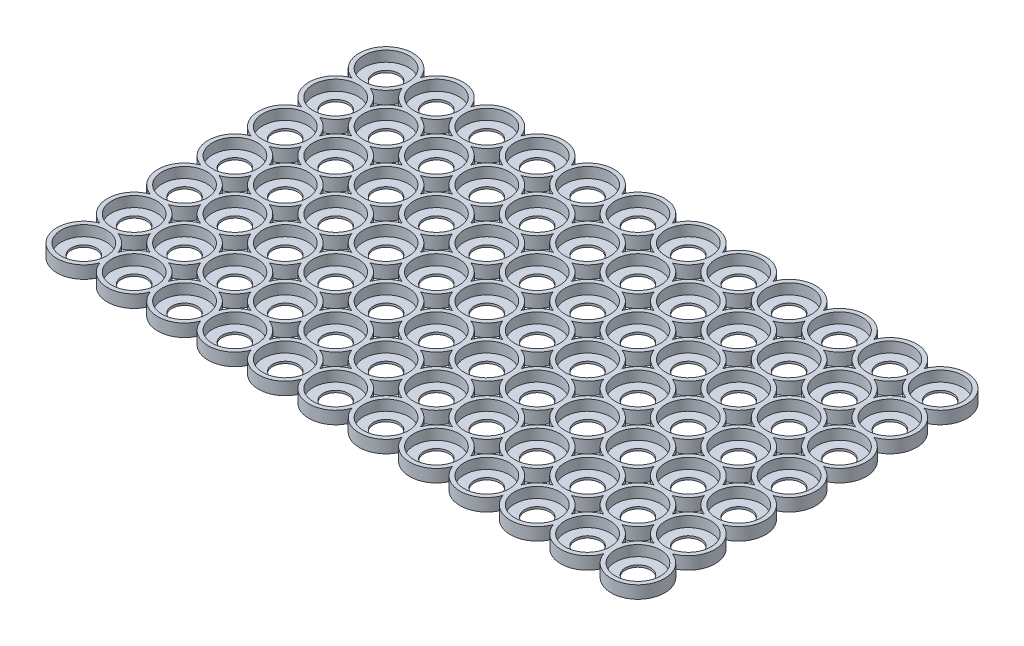
SolidWorks part; units mm, degrees
ref_plane "Front Plane" through (0, 0, 0) normal (0, 0, 1) x (1, 0, 0)
ref_plane "Top Plane" through (0, 0, 0) normal (0, 1, 0) x (1, 0, 0)
ref_plane "Right Plane" through (0, 0, 0) normal (1, 0, 0) x (0, 0, -1)
sketch "Sketch1" plane through (0, 0, 0) normal (1, 0, 0) x (0, 0, -1)
  line L0 (0, 27.0772) -> (0, -22.0037) construction
  line L1 (-12.75, 3) -> (-12.75, -3)
  line L2 (-12.75, -3) -> (-6, -3)
  line L3 (-6, -3) -> (-6, -2)
  line L4 (-6, -2) -> (-10.75, -2)
  line L5 (-10.75, -2) -> (-10.75, 3)
  line L6 (-10.75, 3) -> (-12.75, 3)
  point P5 (-12.75, 0)
  dimension "D1" = 6
  dimension "D2" = 1
  dimension "D3" = 21.5
  dimension "D4" = 12
  dimension "D5" = 2
revolve "Revolve1" add sketch "Sketch1" angle 360 about L0
sketch "Sketch2" plane through (0, -3, 0) normal (0, -1, 0) x (1, 0, 0)
  line L0 (0, 12.1827) -> (0, -11.4982) construction
pattern_linear "LPattern1" count 7 spacing 24 along (0, 0, -1) of "Revolve1"
sketch "Sketch3" plane through (0, -3, 0) normal (0, -1, 0) x (1, 0, 0)
  line L0 (-17.2986, 0) -> (17.8169, 0) construction
pattern_linear "LPattern2" count 12 spacing 24 along (1, 0, 0) of "Revolve1", "LPattern1"
